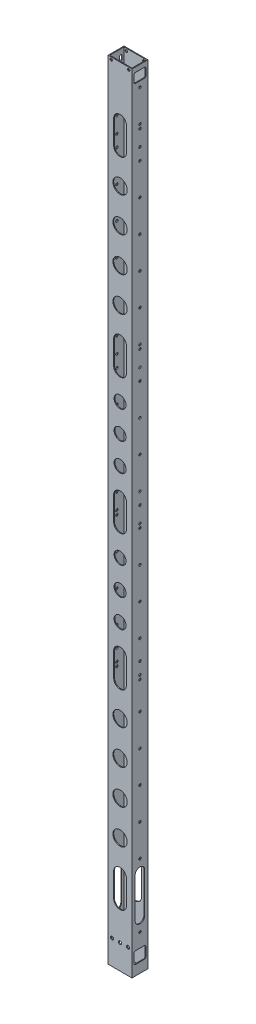
SolidWorks part; units mm, degrees
material "6061 合金"
ref_plane "Front" through (0, 0, 0) normal (0, 0, 1) x (1, 0, 0)
ref_plane "Top" through (0, 0, 0) normal (0, 1, 0) x (1, 0, 0)
ref_plane "Right" through (0, 0, 0) normal (1, 0, 0) x (0, 0, -1)
sketch "草图1" plane through (0, 0, 0) normal (0, 1, 0) x (1, 0, 0)
  line L1 (-15, -10) -> (15, -10)
  line L2 (-15, -10) -> (-15, 10)
  line L3 (-15, 10) -> (15, 10)
  line L4 (15, -10) -> (15, 10)
  line L5 (-15, -10) -> (15, 10) construction
  line L6 (-15, 10) -> (15, -10) construction
  line L7 (-14, -9) -> (14, -9)
  line L8 (-14, -9) -> (-14, 9)
  line L9 (-14, 9) -> (14, 9)
  line L10 (14, -9) -> (14, 9)
  line L11 (-14, -9) -> (14, 9) construction
  line L12 (-14, 9) -> (14, -9) construction
  point P0 (0, 0)
  point P5 (0, 0)
  dimension "D1" = 20
  dimension "D2" = 30
  dimension "D3" = 1
  dimension "D4" = 1
extrude "凸台-拉伸1" add sketch "草图1" along normal blind 980
sketch "草图3" plane through (15, 0, 0) normal (1, 0, 0) x (0, 0, -1)
  line L0 (0, 310) -> (0, 330) construction
  line L1 (0, 0) -> (0, 50000) construction
  line L2 (0, 910) -> (0, 890) construction
  line L4 (-10, 980) -> (10, 980) construction
  line L5 (-10, 490) -> (10, 490) construction
  line L6 (-10, 980) -> (-10, 0) construction
  line L7 (10, 980) -> (10, 0) construction
  line L8 (0, 500) -> (0, 480) construction
  line L9 (0, 670) -> (0, 650) construction
  line L10 (0, 70) -> (0, 90) construction
  circle A4 centre (0, 890) radius 1.5
  circle A5 centre (0, 910) radius 1.5
  circle A10 centre (0, 500) radius 1.5
  circle A11 centre (0, 480) radius 1.5
  circle A12 centre (0, 670) radius 1.5
  circle A13 centre (0, 650) radius 1.5
  circle A14 centre (0, 330) radius 1.5
  circle A15 centre (0, 310) radius 1.5
  circle A16 centre (0, 70) radius 1.5
  circle A17 centre (0, 90) radius 1.5
  dimension "D6" = 3
  dimension "D8" = 3
  dimension "D9" = 3
  dimension "D12" = 70
  dimension "D15" = 20
  dimension "D16" = 3
  dimension "D7" = 3
  dimension "D11" = 10
  dimension "D14" = 3
  dimension "D10" = 20
  dimension "D13" = 20
  dimension "D17" = 220
extrude "切除-拉伸2" cut sketch "草图3" against normal through all
sketch "草图4" plane through (15, 0, 0) normal (1, 0, 0) x (0, 0, -1)
  line L0 (0, 0) -> (0, 50000) construction
  line L1 (-10, 0) -> (10, 0) construction
  line L2 (-10, 980) -> (10, 980) construction
  line L3 (5, 968) -> (5, 972) construction
  line L4 (3.4, 968) -> (3.4, 972)
  line L5 (6.6, 968) -> (6.6, 972)
  line L6 (-5, 968) -> (-5, 972) construction
  line L7 (-3.4, 968) -> (-3.4, 972)
  line L8 (-6.6, 968) -> (-6.6, 972)
  circle A0 centre (-5, 10) radius 1.6 construction
  circle A1 centre (5, 10) radius 1.6 construction
  circle A2 centre (-5, 970) radius 1.6 construction
  circle A3 centre (5, 970) radius 1.6 construction
  arc A4 (3.4, 968) -> (6.6, 968) centre (5, 968) ccw
  arc A5 (6.6, 972) -> (3.4, 972) centre (5, 972) ccw
  arc A6 (-3.4, 968) -> (-6.6, 968) centre (-5, 968) cw
  arc A7 (-6.6, 972) -> (-3.4, 972) centre (-5, 972) cw
  point P17 (5, 970)
  point P24 (-5, 970)
  dimension "D1" = 3.2
  dimension "D4" = 3.2
  dimension "D7" = 1.6
  dimension "D2" = 10
  dimension "D3" = 10
  dimension "D5" = 10
  dimension "D6" = 10
  dimension "D8" = 4
extrude "切除-拉伸3" cut sketch "草图4" against normal through all
sketch "草图5" plane through (15, 0, 0) normal (1, 0, 0) x (0, 0, -1)
  line L0 (0, 0) -> (0, 50000) construction
  line L1 (10, 968) -> (-10, 968) construction
  line L2 (10, 980) -> (10, 0) construction
  line L3 (-10, 980) -> (-10, 0) construction
  line L4 (-10, 980) -> (10, 980) construction
  line L6 (-7.5, 974) -> (7.5, 974)
  line L7 (-7.5, 974) -> (-7.5, 962)
  line L8 (-7.5, 962) -> (7.5, 962)
  line L9 (7.5, 974) -> (7.5, 962)
  line L10 (-7.5, 974) -> (7.5, 962) construction
  line L11 (-7.5, 962) -> (7.5, 974) construction
  point P13 (0, 968)
  dimension "D1" = 12
  dimension "D2" = 12
  dimension "D3" = 15
extrude "切除-拉伸4" cut sketch "草图5" against normal blind 10
sketch "草图6" plane through (0, 0, -10) normal (0, 0, -1) x (-1, 0, 0)
  line L0 (-15, 91.5) -> (-15, 88.5) construction
  line L1 (-15, 71.5) -> (-15, 68.5) construction
  line L2 (-15, 91.5) -> (-15, 88.5) construction
  line L3 (-15, 71.5) -> (-15, 68.5) construction
  line L4 (-15, 891.5) -> (-15, 888.5) construction
  line L5 (-15, 911.5) -> (-15, 908.5) construction
  line L6 (-15, 671.5) -> (-15, 668.5) construction
  line L7 (-15, 651.5) -> (-15, 648.5) construction
  line L8 (-15, 501.5) -> (-15, 498.5) construction
  line L9 (-15, 481.5) -> (-15, 478.5) construction
  line L10 (-15, 331.5) -> (-15, 328.5) construction
  line L11 (-15, 311.5) -> (-15, 308.5) construction
  line L12 (-15, 891.5) -> (-15, 888.5) construction
  line L13 (-15, 911.5) -> (-15, 908.5) construction
  line L14 (-15, 671.5) -> (-15, 668.5) construction
  line L15 (-15, 651.5) -> (-15, 648.5) construction
  line L16 (-15, 501.5) -> (-15, 498.5) construction
  line L17 (-15, 481.5) -> (-15, 478.5) construction
  line L18 (-15, 331.5) -> (-15, 328.5) construction
  line L19 (-15, 311.5) -> (-15, 308.5) construction
  line L20 (0, 65) -> (0, 95) construction
  line L21 (-8, 65) -> (-8, 95)
  line L22 (8, 65) -> (8, 95)
  line L23 (0, 475) -> (0, 505) construction
  line L24 (-15, 88.5) -> (-15, 71.5) construction
  line L25 (-15, 80) -> (-40.807, 80) construction
  line L26 (0, 305) -> (0, 335) construction
  line L27 (-8, 305) -> (-8, 335)
  line L28 (8, 305) -> (8, 335)
  line L29 (0, 65) -> (0, 305) construction
  line L30 (-8, 475) -> (-8, 505)
  line L31 (8, 475) -> (8, 505)
  line L32 (0, 645) -> (0, 675) construction
  line L33 (-8, 645) -> (-8, 675)
  line L34 (8, 645) -> (8, 675)
  line L35 (0, 305) -> (0, 475) construction
  line L36 (0, 885) -> (0, 915) construction
  line L37 (-8, 885) -> (-8, 915)
  line L38 (8, 885) -> (8, 915)
  line L39 (0, 645) -> (0, 885) construction
  line L40 (0, 490) -> (-90.401, 490) construction
  arc A0 (-8, 65) -> (8, 65) centre (0, 65) ccw
  arc A1 (8, 95) -> (-8, 95) centre (0, 95) ccw
  arc A2 (-8, 305) -> (8, 305) centre (0, 305) ccw
  arc A3 (8, 335) -> (-8, 335) centre (0, 335) ccw
  arc A4 (-8, 475) -> (8, 475) centre (0, 475) ccw
  arc A5 (8, 505) -> (-8, 505) centre (0, 505) ccw
  arc A6 (-8, 645) -> (8, 645) centre (0, 645) ccw
  arc A7 (8, 675) -> (-8, 675) centre (0, 675) ccw
  arc A8 (-8, 885) -> (8, 885) centre (0, 885) ccw
  arc A9 (8, 915) -> (-8, 915) centre (0, 915) ccw
  circle A10 centre (0, 135) radius 9
  circle A11 centre (0, 178.3333) radius 9
  circle A12 centre (0, 221.6667) radius 9
  circle A13 centre (0, 265) radius 9
  circle A14 centre (0, 845) radius 9
  circle A16 centre (0, 801.6667) radius 9
  circle A17 centre (0, 758.3333) radius 9
  circle A18 centre (0, 715) radius 9
  circle A19 centre (0, 440) radius 7.5
  circle A20 centre (0, 405) radius 7.5
  circle A21 centre (0, 370) radius 7.5
  circle A22 centre (0, 610) radius 7.5
  circle A23 centre (0, 575) radius 7.5
  circle A24 centre (0, 540) radius 7.5
  point P23 (0, 80)
  point P34 (0, 320)
  point P42 (0, 490)
  point P49 (0, 660)
  point P58 (0, 900)
  dimension "D1" = 8
  dimension "D10" = 18
  dimension "D11" = 40
  dimension "D12" = 40
  dimension "D13" = 43.3333
  dimension "D14" = 40
  dimension "D16" = 40
  dimension "D18" = 35
  dimension "D19" = 35
  dimension "D20" = 35
  dimension "D21" = 15
  dimension "D2" = 30
  dimension "D3" = 2
  dimension "D4" = 240
  dimension "D5" = 3
  dimension "D6" = 170
  dimension "D8" = 240
  dimension "D9" = 4
  dimension "D7" = 2
  dimension "D15" = 4
  dimension "D17" = 3
extrude "切除-拉伸5" cut sketch "草图6" against normal through all
sketch "草图7" plane through (15, 0, 0) normal (1, 0, 0) x (0, 0, -1)
  line L1 (-10, 980) -> (-10, 0) construction
  line L2 (-10, 0) -> (10, 0) construction
  line L3 (0, 0) -> (0, 24.669) construction
  line L4 (-10, 980) -> (10, 980) construction
  circle A0 centre (-5, 5) radius 1.5
  circle A1 centre (5, 5) radius 1.5
  circle A2 centre (-5, 975) radius 1.5
  circle A3 centre (5, 975) radius 1.5
  dimension "D1" = 5
  dimension "D2" = 5
  dimension "D3" = 3
  dimension "D4" = 5
  dimension "D5" = 5
  dimension "D6" = 3
extrude "切除-拉伸6" [suppressed] cut sketch "草图7" against normal through all
sketch "草图9" plane through (0, 0, 10) normal (0, 0, 1) x (1, 0, 0)
  line L0 (15, 980) -> (15, 0) construction
  line L1 (-15, 0) -> (15, 0) construction
  line L2 (0, 0) -> (0, 1062.0992) construction
  line L3 (-15, 980) -> (15, 980) construction
  circle A0 centre (11, 3) radius 1.5 construction
  circle A1 centre (11, 977) radius 1.5
  circle A2 centre (-11, 3) radius 1.5 construction
  circle A3 centre (-11, 977) radius 1.5
  dimension "D3" = 3
  dimension "D4" = 4
  dimension "D5" = 3
  dimension "D1" = 4
  dimension "D2" = 3
extrude "切除-拉伸7" cut sketch "草图9" against normal through all
sketch "草图13" plane through (0, 0, 0) normal (0, -1, 0) x (1, 0, 0)
  line L4 (15, -10) -> (15, 10)
  line L5 (15, 10) -> (-15, 10)
  line L6 (-15, 10) -> (-15, -10)
  line L7 (-15, -10) -> (15, -10)
  line L8 (15, -10) -> (15, 10)
  line L9 (15, 10) -> (-15, 10)
  line L10 (-15, 10) -> (-15, -10)
  line L11 (-15, -10) -> (15, -10)
  line L12 (14, 9) -> (-14, 9)
  line L13 (14, -9) -> (14, 9)
  line L14 (-14, -9) -> (14, -9)
  line L15 (-14, 9) -> (-14, -9)
  line L16 (14, 9) -> (-14, 9)
  line L17 (14, -9) -> (14, 9)
  line L18 (-14, -9) -> (14, -9)
  line L19 (-14, 9) -> (-14, -9)
  dimension "D1" = 0
  dimension "D2" = 0
extrude "凸台-拉伸2" add sketch "草图13" along normal blind 10
sketch "草图11" plane through (-14, 0, 0) normal (1, 0, 0) x (0, 0, -1)
  line L0 (0, 0) -> (0, 111.3677) construction
  line L1 (-5, 5) -> (-5, 15) construction
  line L2 (-6.6, 5) -> (-6.6, 15)
  line L3 (-3.4, 5) -> (-3.4, 15)
  line L4 (5, 5) -> (5, 15) construction
  line L5 (6.6, 5) -> (6.6, 15)
  line L6 (3.4, 5) -> (3.4, 15)
  line L8 (10, -10) -> (-10, -10) construction
  arc A0 (-6.6, 5) -> (-3.4, 5) centre (-5, 5) ccw
  arc A1 (-3.4, 15) -> (-6.6, 15) centre (-5, 15) ccw
  arc A2 (6.6, 5) -> (3.4, 5) centre (5, 5) cw
  arc A3 (3.4, 15) -> (6.6, 15) centre (5, 15) cw
  point P5 (-5, 10)
  point P12 (5, 10)
  dimension "D4" = 1.6
  dimension "D1" = 10
  dimension "D2" = 20
  dimension "D3" = 10
extrude "切除-拉伸8" cut sketch "草图11" against normal blind 60
sketch "草图15" plane through (15, 0, 0) normal (1, 0, 0) x (0, 0, -1)
  line L0 (0, -10) -> (0, 26.437) construction
  line L1 (10, -10) -> (-10, -10) construction
  line L3 (-7.5, 17.5) -> (7.5, 17.5)
  line L4 (-7.5, 17.5) -> (-7.5, 2.5)
  line L5 (-7.5, 2.5) -> (7.5, 2.5)
  line L6 (7.5, 17.5) -> (7.5, 2.5)
  line L7 (-7.5, 17.5) -> (7.5, 2.5) construction
  line L8 (-7.5, 2.5) -> (7.5, 17.5) construction
  point P5 (0, 10)
  dimension "D1" = 20
  dimension "D2" = 15
  dimension "D3" = 15
extrude "切除-拉伸10" cut sketch "草图15" against normal blind 5
fillet "圆角1" radius 2 4 edges at (14.5, 2.5, -7.5) (14.5, 2.5, 7.5) (14.5, 17.5, -7.5) (14.5, 17.5, 7.5)
sketch "草图16" plane through (0, 0, 10) normal (0, 0, 1) x (1, 0, 0)
  line L0 (0, -10) -> (0, 90.7842) construction
  line L1 (15, -10) -> (-15, -10) construction
  circle A0 centre (10, 21) radius 2
  circle A1 centre (0, 21) radius 2
  circle A2 centre (-10, 21) radius 2
  dimension "D1" = 31
  dimension "D2" = 4
  dimension "D3" = 20
extrude "切除-拉伸11" cut sketch "草图16" against normal blind 90
fillet "圆角2" radius 2 4 edges at (14.5, 962, -7.5) (14.5, 962, 7.5) (14.5, 974, 7.5) (14.5, 974, -7.5)
sketch "草图17" plane through (15, 0, 0) normal (1, 0, 0) x (0, 0, -1)
  line L0 (-10, 980) -> (10, 980) construction
  circle A0 centre (0, 955) radius 1.5
  circle A1 centre (0, 915) radius 1.5
  circle A2 centre (0, 875) radius 1.5
  circle A3 centre (0, 835) radius 1.5
  circle A4 centre (0, 795) radius 1.5
  circle A5 centre (0, 755) radius 1.5
  circle A6 centre (0, 715) radius 1.5
  circle A7 centre (0, 675) radius 1.5
  circle A8 centre (0, 635) radius 1.5
  circle A9 centre (0, 595) radius 1.5
  circle A10 centre (0, 555) radius 1.5
  circle A11 centre (0, 515) radius 1.5
  circle A12 centre (0, 475) radius 1.5
  circle A13 centre (0, 435) radius 1.5
  circle A14 centre (0, 395) radius 1.5
  circle A15 centre (0, 355) radius 1.5
  circle A16 centre (0, 315) radius 1.5
  circle A17 centre (0, 275) radius 1.5
  circle A18 centre (0, 235) radius 1.5
  circle A19 centre (0, 195) radius 1.5
  circle A20 centre (0, 155) radius 1.5
  circle A21 centre (0, 115) radius 1.5
  circle A22 centre (0, 75) radius 1.5
  circle A23 centre (0, 35) radius 1.5
  dimension "D1" = 3
  dimension "D3" = 25
  dimension "D2" = 24
extrude "切除-拉伸12" cut sketch "草图17" against normal blind 40
sketch "草图20" plane through (15, 0, 0) normal (1, 0, 0) x (0, 0, -1)
  line L0 (0, 0) -> (0, 121.9481) construction
  line L1 (0, 50) -> (0, 100) construction
  line L2 (-6, 50) -> (-6, 100)
  line L3 (6, 50) -> (6, 100)
  line L4 (10, -10) -> (-10, -10) construction
  arc A0 (-6, 50) -> (6, 50) centre (0, 50) ccw
  arc A1 (6, 100) -> (-6, 100) centre (0, 100) ccw
  point P5 (0, 75)
  dimension "D2" = 6
  dimension "D3" = 60
  dimension "D1" = 50
extrude "切除-拉伸15" cut sketch "草图20" against normal blind 51
